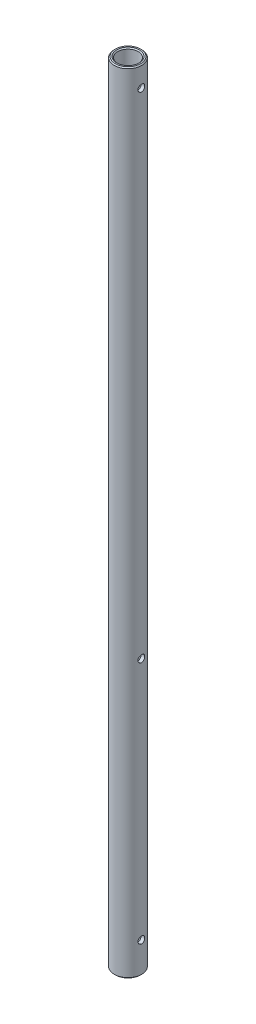
SolidWorks part; units mm, degrees
material "AISI 304"
ref_plane "Спереди" through (0, 0, 0) normal (0, 0, 1) x (1, 0, 0)
ref_plane "Сверху" through (0, 0, 0) normal (0, 1, 0) x (1, 0, 0)
ref_plane "Справа" through (0, 0, 0) normal (1, 0, 0) x (0, 0, -1)
other "Configuration Table"
sketch "Эскиз1" plane through (0, 0, 0) normal (0, 1, 0) x (1, 0, 0)
  circle A0 centre (0, 0) radius 4
  circle A1 centre (0, 0) radius 3
  dimension "D1" = 8
  dimension "D2" = 6
extrude "Бобышка-Вытянуть1" add sketch "Эскиз1" along normal blind 230
chamfer "Фаска1" distance 0.3 angle 45 4 edges at (0, 230, 3) (0, 0, 3) (0, 0, 4) (0, 230, 4)
sketch "Эскиз2" plane through (0, 0, 0) normal (1, 0, 0) x (0, 0, -1)
  circle A0 centre (0, 9) radius 1 construction
  circle A1 centre (0, 9) radius 1
extrude "Вырез-Вытянуть1" cut sketch "Эскиз2" against normal through all both and the other way through all
sketch "Эскиз3" plane through (0, 0, 0) normal (1, 0, 0) x (0, 0, -1)
  circle A0 centre (0, 80) radius 1.25 construction
  circle A3 centre (0, 9) radius 1 construction
  circle A4 centre (0, 9) radius 1 construction
  circle A5 centre (0, 80) radius 1.25 construction
  circle A6 centre (0, 80) radius 1
  dimension "D1" = 2
extrude "Вырез-Вытянуть2" cut sketch "Эскиз3" against normal through all both and the other way through all
sketch "Эскиз4" plane through (0, 0, 0) normal (1, 0, 0) x (0, 0, -1)
  line L0 (0, -1000) -> (0, 49000) construction
  circle A0 centre (0, 224) radius 1
  dimension "D1" = 2
  dimension "D2" = 224
extrude "Вырез-Вытянуть3" cut sketch "Эскиз4" against normal through all both and the other way through all
